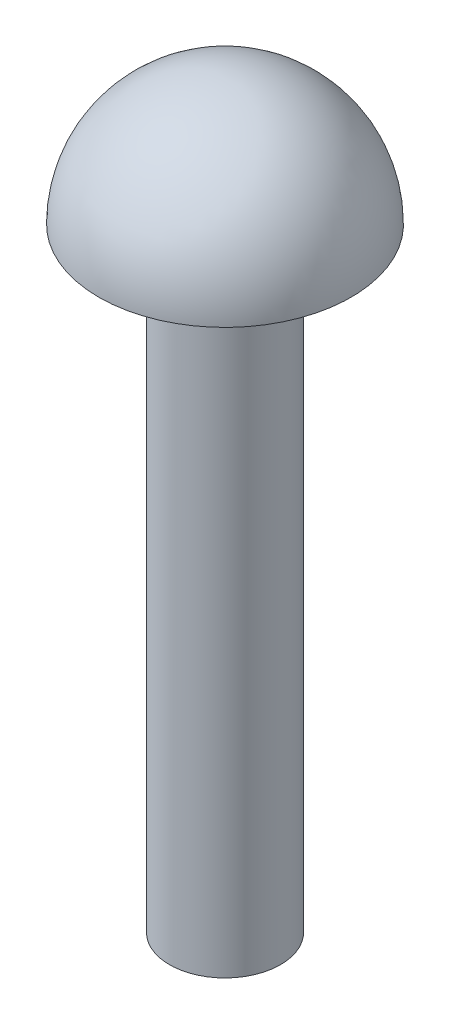
SolidWorks part; units mm, degrees
ref_plane "Front Plane" through (0, 0, 0) normal (0, 0, 1) x (1, 0, 0)
ref_plane "Top Plane" through (0, 0, 0) normal (0, 1, 0) x (1, 0, 0)
ref_plane "Right Plane" through (0, 0, 0) normal (1, 0, 0) x (0, 0, -1)
sketch "Sketch2" plane through (0, 0, 0) normal (0, 1, 0) x (1, 0, 0)
  circle A0 centre (0, 0) radius 11
extrude "Boss-Extrude1" add sketch "Sketch2" along normal blind 183
sketch "Sketch3" plane through (0, 183, 0) normal (0, 1, 0) x (1, 0, 0)
  circle A0 centre (0, 0) radius 25
extrude "Boss-Extrude2" add sketch "Sketch3" along normal blind 25 contours A0
fillet "Fillet1" radius 25 1 edges at (0, 208, 25)
sketch "Sketch4" plane through (0, 0, 0) normal (0, -1, 0) x (1, 0, 0)
  circle A0 centre (0, 0) radius 11
extrude "Boss-Extrude5" add sketch "Sketch4" along normal blind 85
thread "Thread3" pitch 5 method cut profile "Thread Profile5" start angle 5, offset 4, length 15, pitch 5, diameter 22
ref_plane "Plane5" through (10.9581, -89, -0.9587) normal (0.0872, 0, 0.9962) x (0.9962, 0, -0.0872)
sketch "Thread Profile5" plane through (10.9581, -89, -0.9587) normal (0.0872, 0, 0.9962) x (0.9962, 0, -0.0872)
  line L0 (0, 0) -> (0, 5) construction
  line L11 (0, 0) -> (0, 4.375)
  line L12 (0, 4.375) -> (-2.7063, 2.8125)
  line L13 (-2.7063, 2.8125) -> (-2.7063, 1.5625)
  line L15 (-2.7063, 1.5625) -> (0, 0)
  line L17 (-2.7063, 2.1875) -> (0, 2.1875) construction
  point P2 (0, 0)
  dimension "Pitch" = 5
  dimension "Profile_Angle" = 60
  dimension "Profile_Land" = 1.25
  dimension "Profile_Height" = 2.7063
sketch "Sketch35" plane through (0, -85, 0) normal (0, -1, 0) x (-1, 0, 0)
  circle A0 centre (0, 0) radius 19.9978
extrude "Cut-Extrude3" cut sketch "Sketch35" along normal blind 70 contours A0 rebuild error yes
sketch "Sketch36" plane through (0, -85, 0) normal (0, -1, 0) x (-1, 0, 0)
  circle A0 centre (0, 0) radius 19.4023
extrude "Cut-Extrude4" cut sketch "Sketch36" against normal blind 146.5
sketch "Sketch37" plane through (0, 61.5, 0) normal (0, -1, 0) x (1, 0, 0)
  circle A0 centre (0, 0) radius 7.5
extrude "Cut-Extrude5" cut sketch "Sketch37" against normal blind 30
